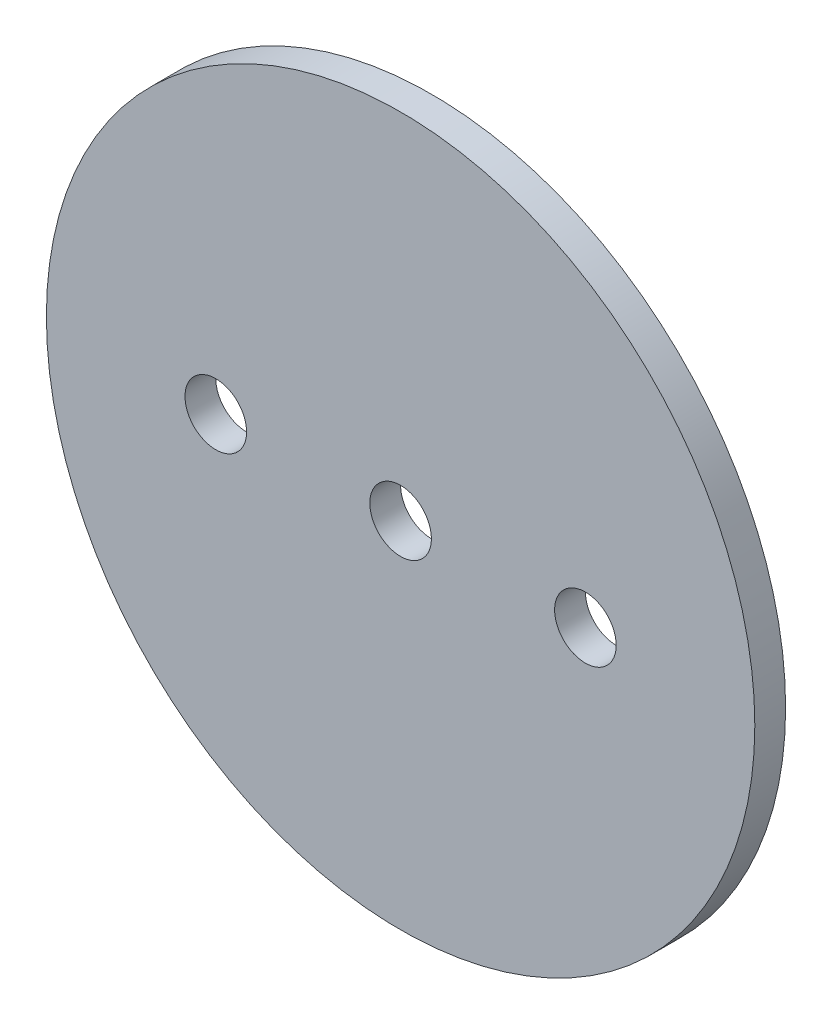
SolidWorks part; units mm, degrees
ref_plane "Front Plane" through (0, 0, 0) normal (0, 0, 1) x (1, 0, 0)
ref_plane "Top Plane" through (0, 0, 0) normal (0, 1, 0) x (1, 0, 0)
ref_plane "Right Plane" through (0, 0, 0) normal (1, 0, 0) x (0, 0, -1)
sketch "Sketch1" plane through (0, 0, 0) normal (0, 0, 1) x (1, 0, 0)
  circle A0 centre (0, 0) radius 36.5125
  dimension "D1" = 73.025
extrude "Boss-Extrude1" add sketch "Sketch1" along normal mid plane 3.175
sketch "Sketch2" plane through (0, 0, 1.5875) normal (0, 0, 1) x (1, 0, 0)
  line L0 (-1000, 0) -> (49000, 0) construction
  point P1 (0, 0)
  point P4 (19.05, 0)
  point P5 (-19.05, 0)
  dimension "D1" = 19.05
  dimension "D2" = 38.1
hole_wizard "1/4 (0.25) Diameter Hole1" positions "Sketch2" profile "Sketch3" hole size "1/4" standard "ANSI Inch" end condition through all
sketch "Sketch3" plane through (-19.05, 0, 1.5875) normal (1, 0, 0) x (0, -1, 0)
  line L0 (0, 0) -> (0, 3.175)
  line L1 (0, 3.175) -> (3.175, 3.175)
  line L2 (3.175, 3.175) -> (3.175, 0)
  line L5 (3.175, 0) -> (0, 0)
  line L11 (0, -6.35) -> (0, 107.95) construction
  dimension "Thru Hole Dia." = 6.35
  dimension "Thru Hole Depth" = 3.175
equation "\"AIRFRAME_OD\"= 3.091in"
equation "\"AIRFRAME_ID\"= 3.00in"
equation "\"FLAT_T\"= 0.125in"
equation "\"NOSE_EXP_L\"= 3.5in"
equation "\"NOSE_SHOULDER_L\"= 5in"
equation "\"MAIN_L\"= 30in"
equation "\"RECO_COUP_L\"= 6in"
equation "\"RECO_SWITCH_L\"= 1.5in"
equation "\"DROGUE_L\"= 14in"
equation "\"ATS_FORE_COUP_L\"= 4in"
equation "\"ATS_AFT_COUP_L\"= 2.5in"
equation "\"LOWER_L\"= 16in"
equation "\"FIN_N\"= 4"
equation "\"CR_AFT_X\"= 0.5in"
equation "\"CR_FORE_X\"= 6in"
equation "\"FIN_ROOT\"= 5in"
equation "\"FIN_X\"= 0.75in"
equation "\"MOTOR_OD\"= 2.25in"
equation "\"MOTOR_ID\"= 2.126in"
equation "\"COUPLER_OD\"= 2.998in"
equation "\"COUPLER_ID\"= 2.875in"
equation "\"D1@Sketch1\"=\"COUPLER_ID\""
equation "\"D1@Boss-Extrude1\"=\"FLAT_T\""
equation "\"RECO_ROD_X\"= 1.5in"
equation "\"ATS_ROD_X\"= 2in"
equation "\"D1@Sketch2\"=\"RECO_ROD_X\"*0.5"
equation "\"D2@Sketch2\"=\"RECO_ROD_X\""
